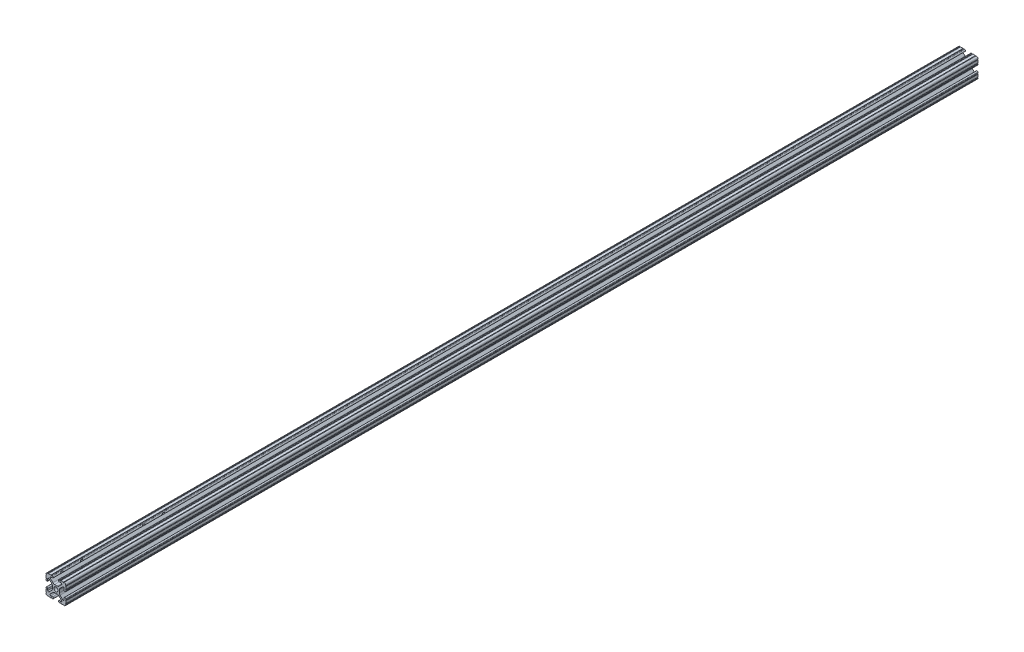
SolidWorks part; units mm, degrees
ref_plane "Front Plane" through (0, 0, 0) normal (0, 0, 1) x (1, 0, 0)
ref_plane "Top Plane" through (0, 0, 0) normal (0, 1, 0) x (1, 0, 0)
ref_plane "Right Plane" through (0, 0, 0) normal (1, 0, 0) x (0, 0, -1)
ref_plane "Plane1" through (0, 0, -2463.8) normal (0, 0, -1) x (-1, 0, 0)
sketch "Sketch1" plane through (0, 0, -2463.8) normal (0, 0, -1) x (-1, 0, 0)
  line L0 (12.7, -9.5504) -> (12.7, -6.3331)
  line L1 (12.7, -5.3171) -> (12.7, -4.3434)
  line L2 (10.4902, -4.3434) -> (10.4902, -6.4748)
  line L3 (8.7558, -7.1932) -> (5.4257, -3.8632)
  line L4 (4.4958, -1.6181) -> (4.4958, 1.6181)
  line L5 (5.4257, 3.8632) -> (8.7558, 7.1932)
  line L6 (10.4902, 6.4748) -> (10.4902, 4.3434)
  line L7 (12.7, 4.3434) -> (12.7, 5.3171)
  line L8 (12.7, 6.3331) -> (12.7, 9.5504)
  line L9 (9.5504, 12.7) -> (6.3331, 12.7)
  line L10 (5.3171, 12.7) -> (4.3434, 12.7)
  line L11 (4.3434, 10.4902) -> (6.4748, 10.4902)
  line L12 (7.1932, 8.7558) -> (3.8632, 5.4257)
  line L13 (1.6181, 4.4958) -> (-1.6181, 4.4958)
  line L14 (-3.8632, 5.4257) -> (-7.1932, 8.7558)
  line L15 (-6.4748, 10.4902) -> (-4.3434, 10.4902)
  line L16 (-4.3434, 12.7) -> (-5.3171, 12.7)
  line L17 (-6.3331, 12.7) -> (-9.5504, 12.7)
  line L18 (-12.7, 9.5504) -> (-12.7, 6.3331)
  line L19 (-12.7, 5.3171) -> (-12.7, 4.3434)
  line L20 (-10.4902, 4.3434) -> (-10.4902, 6.4748)
  line L21 (-8.7558, 7.1932) -> (-5.4257, 3.8632)
  line L22 (-4.4958, 1.6181) -> (-4.4958, -1.6181)
  line L23 (-5.4257, -3.8632) -> (-8.7558, -7.1932)
  line L24 (-10.4902, -6.4748) -> (-10.4902, -4.3434)
  line L25 (-12.7, -4.3434) -> (-12.7, -5.3171)
  line L26 (-12.7, -6.3331) -> (-12.7, -9.5504)
  line L27 (-9.5504, -12.7) -> (-6.3331, -12.7)
  line L28 (-5.3171, -12.7) -> (-4.3434, -12.7)
  line L29 (-4.3434, -10.4902) -> (-6.4748, -10.4902)
  line L30 (-7.1932, -8.7558) -> (-3.8632, -5.4257)
  line L31 (-1.6181, -4.4958) -> (1.6181, -4.4958)
  line L32 (3.8632, -5.4257) -> (7.1932, -8.7558)
  line L33 (6.4748, -10.4902) -> (4.3434, -10.4902)
  line L34 (4.3434, -12.7) -> (5.3171, -12.7)
  line L35 (6.3331, -12.7) -> (9.5504, -12.7)
  arc A0 (12.6998, -10.5664) -> (12.7, -9.5504) centre (12.7, -10.0584) cw
  arc A1 (12.7, -6.3331) -> (12.7, -5.3171) centre (12.7, -5.8251) cw
  arc A2 (12.7, -4.3434) -> (10.4902, -4.3434) centre (11.5951, -4.3434) ccw
  arc A3 (10.4902, -6.4748) -> (8.7558, -7.1932) centre (9.4742, -6.4748) cw
  arc A4 (5.4257, -3.8632) -> (4.4958, -1.6181) centre (7.6708, -1.6181) cw
  arc A5 (4.4958, 1.6181) -> (5.4257, 3.8632) centre (7.6708, 1.6181) cw
  arc A6 (8.7558, 7.1932) -> (10.4902, 6.4748) centre (9.4742, 6.4748) cw
  arc A7 (10.4902, 4.3434) -> (12.7, 4.3434) centre (11.5951, 4.3434) ccw
  arc A8 (12.7, 5.3171) -> (12.7, 6.3331) centre (12.7, 5.8251) cw
  arc A9 (12.7, 9.5504) -> (12.6998, 10.5664) centre (12.7, 10.0584) cw
  arc A10 (12.6998, 10.5664) -> (10.5664, 12.6998) centre (10.5918, 10.5918) ccw
  arc A11 (10.5664, 12.6998) -> (9.5504, 12.7) centre (10.0584, 12.7) cw
  arc A12 (6.3331, 12.7) -> (5.3171, 12.7) centre (5.8251, 12.7) cw
  arc A13 (4.3434, 12.7) -> (4.3434, 10.4902) centre (4.3434, 11.5951) ccw
  arc A14 (6.4748, 10.4902) -> (7.1932, 8.7558) centre (6.4748, 9.4742) cw
  arc A15 (3.8632, 5.4257) -> (1.6181, 4.4958) centre (1.6181, 7.6708) cw
  arc A16 (-1.6181, 4.4958) -> (-3.8632, 5.4257) centre (-1.6181, 7.6708) cw
  arc A17 (-7.1932, 8.7558) -> (-6.4748, 10.4902) centre (-6.4748, 9.4742) cw
  arc A18 (-4.3434, 10.4902) -> (-4.3434, 12.7) centre (-4.3434, 11.5951) ccw
  arc A19 (-5.3171, 12.7) -> (-6.3331, 12.7) centre (-5.8251, 12.7) cw
  arc A20 (-9.5504, 12.7) -> (-10.5664, 12.6998) centre (-10.0584, 12.7) cw
  arc A21 (-10.5664, 12.6998) -> (-12.6998, 10.5664) centre (-10.5918, 10.5918) ccw
  arc A22 (-12.6998, 10.5664) -> (-12.7, 9.5504) centre (-12.7, 10.0584) cw
  arc A23 (-12.7, 6.3331) -> (-12.7, 5.3171) centre (-12.7, 5.8251) cw
  arc A24 (-12.7, 4.3434) -> (-10.4902, 4.3434) centre (-11.5951, 4.3434) ccw
  arc A25 (-10.4902, 6.4748) -> (-8.7558, 7.1932) centre (-9.4742, 6.4748) cw
  arc A26 (-5.4257, 3.8632) -> (-4.4958, 1.6181) centre (-7.6708, 1.6181) cw
  arc A27 (-4.4958, -1.6181) -> (-5.4257, -3.8632) centre (-7.6708, -1.6181) cw
  arc A28 (-8.7558, -7.1932) -> (-10.4902, -6.4748) centre (-9.4742, -6.4748) cw
  arc A29 (-10.4902, -4.3434) -> (-12.7, -4.3434) centre (-11.5951, -4.3434) ccw
  arc A30 (-12.7, -5.3171) -> (-12.7, -6.3331) centre (-12.7, -5.8251) cw
  arc A31 (-12.7, -9.5504) -> (-12.6998, -10.5664) centre (-12.7, -10.0584) cw
  arc A32 (-12.6998, -10.5664) -> (-10.5664, -12.6998) centre (-10.5918, -10.5918) ccw
  arc A33 (-10.5664, -12.6998) -> (-9.5504, -12.7) centre (-10.0584, -12.7) cw
  arc A34 (-6.3331, -12.7) -> (-5.3171, -12.7) centre (-5.8251, -12.7) cw
  arc A35 (-4.3434, -12.7) -> (-4.3434, -10.4902) centre (-4.3434, -11.5951) ccw
  arc A36 (-6.4748, -10.4902) -> (-7.1932, -8.7558) centre (-6.4748, -9.4742) cw
  arc A37 (-3.8632, -5.4257) -> (-1.6181, -4.4958) centre (-1.6181, -7.6708) cw
  arc A38 (1.6181, -4.4958) -> (3.8632, -5.4257) centre (1.6181, -7.6708) cw
  arc A39 (7.1932, -8.7558) -> (6.4748, -10.4902) centre (6.4748, -9.4742) cw
  arc A40 (4.3434, -10.4902) -> (4.3434, -12.7) centre (4.3434, -11.5951) ccw
  arc A41 (5.3171, -12.7) -> (6.3331, -12.7) centre (5.8251, -12.7) cw
  arc A42 (9.5504, -12.7) -> (10.5664, -12.6998) centre (10.0584, -12.7) cw
  arc A43 (10.5664, -12.6998) -> (12.6998, -10.5664) centre (10.5918, -10.5918) ccw
  circle A44 centre (0, 0) radius 2.6035
extrude "Boss-Extrude1" add sketch "Sketch1" along normal blind 1168.4
sketch "Sketch2" plane through (0, 4.4958, 0) normal (0, 1, 0) x (1, 0, 0)
  circle A2 centre (0, 2500.3125) radius 3.7719
  circle A3 centre (0, 2474.9125) radius 3.7719
  circle A4 centre (0, 2605.0875) radius 3.7719
  circle A5 centre (0, 2579.6875) radius 3.7719
  dimension "D1" = 7.5438
  dimension "D2" = 7.5438
  dimension "D3" = 7.5438
  dimension "D4" = 7.5438
extrude "Cut-Extrude1" cut sketch "Sketch2" against normal up to surface and the other way up to surface up to face at (-7.9417, -12.7, -3048) other way up to face at (-7.9417, 12.7, -3048)
